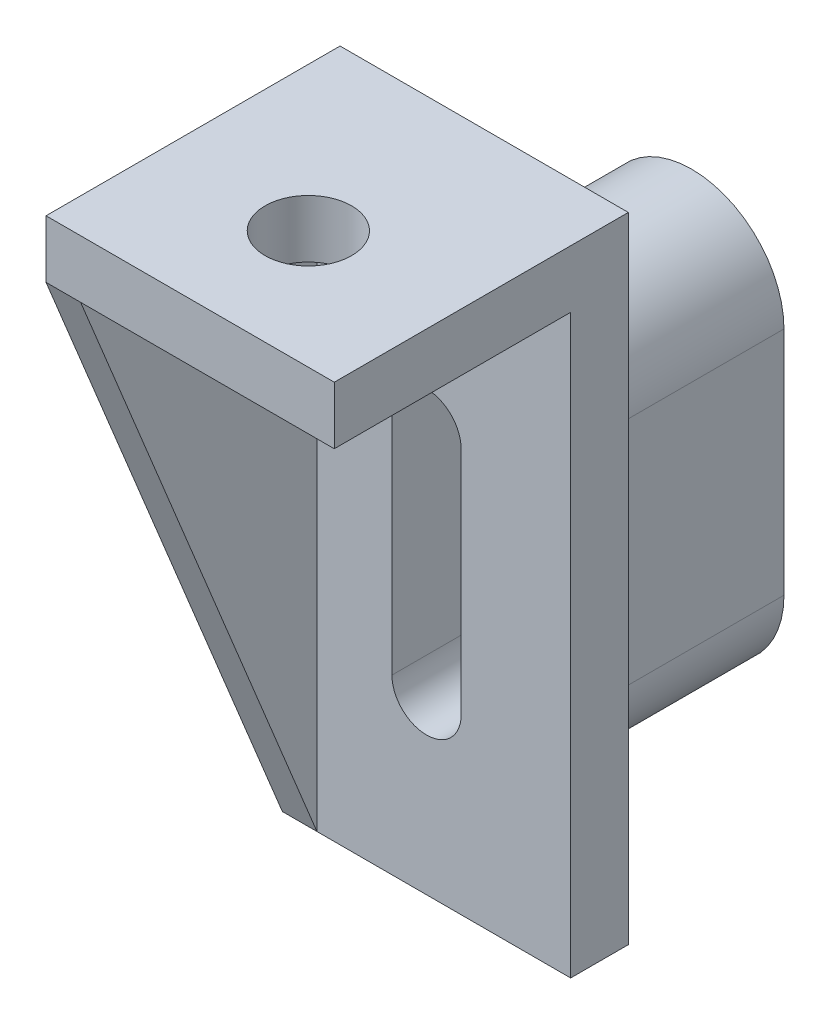
SolidWorks part; units mm, degrees
ref_plane "Спереди" through (0, 0, 0) normal (0, 0, 1) x (1, 0, 0)
ref_plane "Сверху" through (0, 0, 0) normal (0, 1, 0) x (1, 0, 0)
ref_plane "Справа" through (0, 0, 0) normal (1, 0, 0) x (0, 0, -1)
sketch "Эскиз1" plane through (0, 0, 0) normal (0, 0, 1) x (1, 0, 0)
  line L0 (0, -20) -> (0, 20) construction
  line L1 (-25, -50) -> (25, -50)
  line L2 (-25, -50) -> (-25, 50)
  line L3 (-25, 50) -> (25, 50)
  line L4 (25, -50) -> (25, 50)
  line L5 (-25, -50) -> (25, 50) construction
  line L6 (-25, 50) -> (25, -50) construction
  line L7 (-6, -20) -> (-6, 20)
  line L8 (6, -20) -> (6, 20)
  line L9 (-16, -20) -> (-16, 20)
  line L10 (16, -20) -> (16, 20)
  arc A0 (-6, -20) -> (6, -20) centre (0, -20) ccw
  arc A1 (6, 20) -> (-6, 20) centre (0, 20) ccw
  arc A2 (16, 20) -> (-16, 20) centre (0, 20) ccw
  arc A3 (-16, -20) -> (16, -20) centre (0, -20) ccw
  point P0 (0, 0)
  point P8 (0, 0)
  dimension "D3" = 6
  dimension "D1" = 50
  dimension "D2" = 100
  dimension "D4" = 40
  dimension "D5" = 10
extrude "Бобышка-Вытянуть1" add sketch "Эскиз1" along normal blind 10 contours L9 A3 L10 A2 A1 L8 A0 L7 | L1 L4 L3 L2 A3 L9 A2 L10 region at (-23.882, 0, 0) region at (-15.2121, 0, 0)
extrude "Бобышка-Вытянуть2" add sketch "Эскиз1<3>" against normal blind 36 contours L9 A3 L10 A2 A1 L8 A0 L7 region at (-15.2121, 0, 0)
sketch "Эскиз1<3>" plane through (0, 0, 0) normal (0, 0, 1) x (1, 0, 0) same geometry as "Эскиз1"
sketch "Эскиз2" plane through (0, 0, 0) normal (0, 0, -1) x (-1, 0, 0)
  line L0 (25, -50) -> (25, 50) construction
  line L1 (-25, 50) -> (25, 50)
  line L2 (-25, 50) -> (-25, 60)
  line L3 (-25, 60) -> (25, 60)
  line L4 (25, 50) -> (25, 60)
  dimension "D1" = 10
extrude "Бобышка-Вытянуть3" add sketch "Эскиз2" against normal blind 51
sketch "Эскиз3" plane through (0, 50, 0) normal (0, -1, 0) x (1, 0, 0)
  line L0 (0, 51) -> (0, 10) construction
  line L1 (25, 51) -> (-25, 51) construction
  line L2 (-25, 10) -> (25, 10) construction
  circle A0 centre (0, 30.5) radius 7.5
  dimension "D1" = 15
extrude "Вырез-Вытянуть1" cut sketch "Эскиз3" against normal through all
sketch "Эскиз4" plane through (-25, 0, 0) normal (-1, 0, 0) x (0, 0, 1)
  line L0 (51, 50) -> (10, -50)
  line L1 (10, -50) -> (10, 50)
  line L2 (10, 50) -> (51, 50)
extrude "Бобышка-Вытянуть4" add sketch "Эскиз4" against normal blind 6
